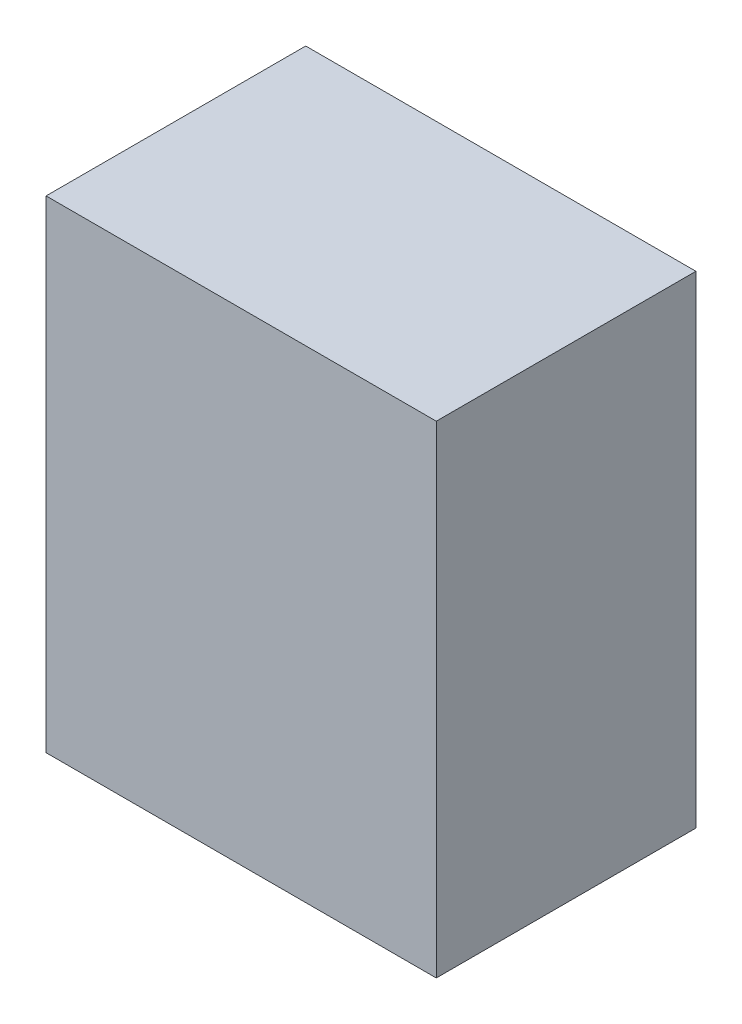
SolidWorks part; units mm, degrees
ref_plane "Front Plane" through (0, 0, 0) normal (0, 0, 1) x (1, 0, 0)
ref_plane "Top Plane" through (0, 0, 0) normal (0, 1, 0) x (1, 0, 0)
ref_plane "Right Plane" through (0, 0, 0) normal (1, 0, 0) x (0, 0, -1)
sketch "Sketch1" plane through (0, 0, 0) normal (0, 0, 1) x (1, 0, 0)
  line L1 (-13.4576, 22.5506) -> (25.0967, 22.5506)
  line L2 (-13.4576, 22.5506) -> (-13.4576, -25.0967)
  line L3 (-13.4576, -25.0967) -> (25.0967, -25.0967)
  line L4 (25.0967, 22.5506) -> (25.0967, -25.0967)
extrude "Boss-Extrude1" add sketch "Sketch1" along normal blind 25.654
